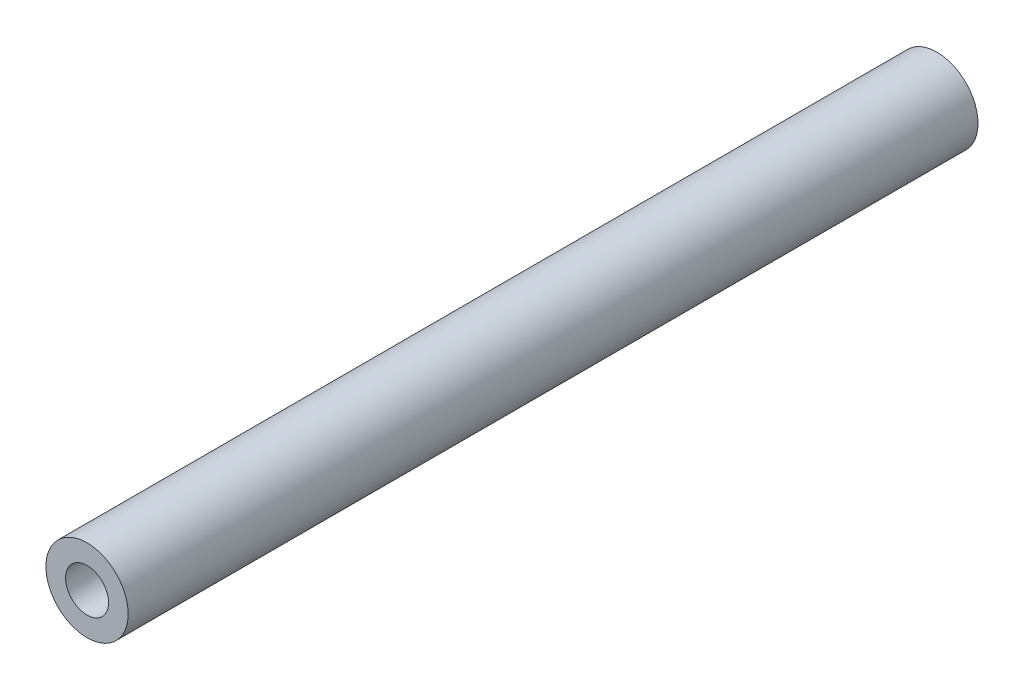
SolidWorks part; units mm, degrees
material "6061-T6 (SS)"
ref_plane "Front Plane" through (0, 0, 0) normal (0, 0, 1) x (1, 0, 0)
ref_plane "Top Plane" through (0, 0, 0) normal (0, 1, 0) x (1, 0, 0)
ref_plane "Right Plane" through (0, 0, 0) normal (1, 0, 0) x (0, 0, -1)
sketch "Sketch1" plane through (0, 0, 0) normal (0, 0, 1) x (1, 0, 0)
  circle A0 centre (0, 0) radius 4.7625
  circle A1 centre (0, 0) radius 2.4892
  dimension "D1" = 4.9784
  dimension "D2" = 9.525
extrude "Boss-Extrude1" add sketch "Sketch1" along normal blind 98.425
